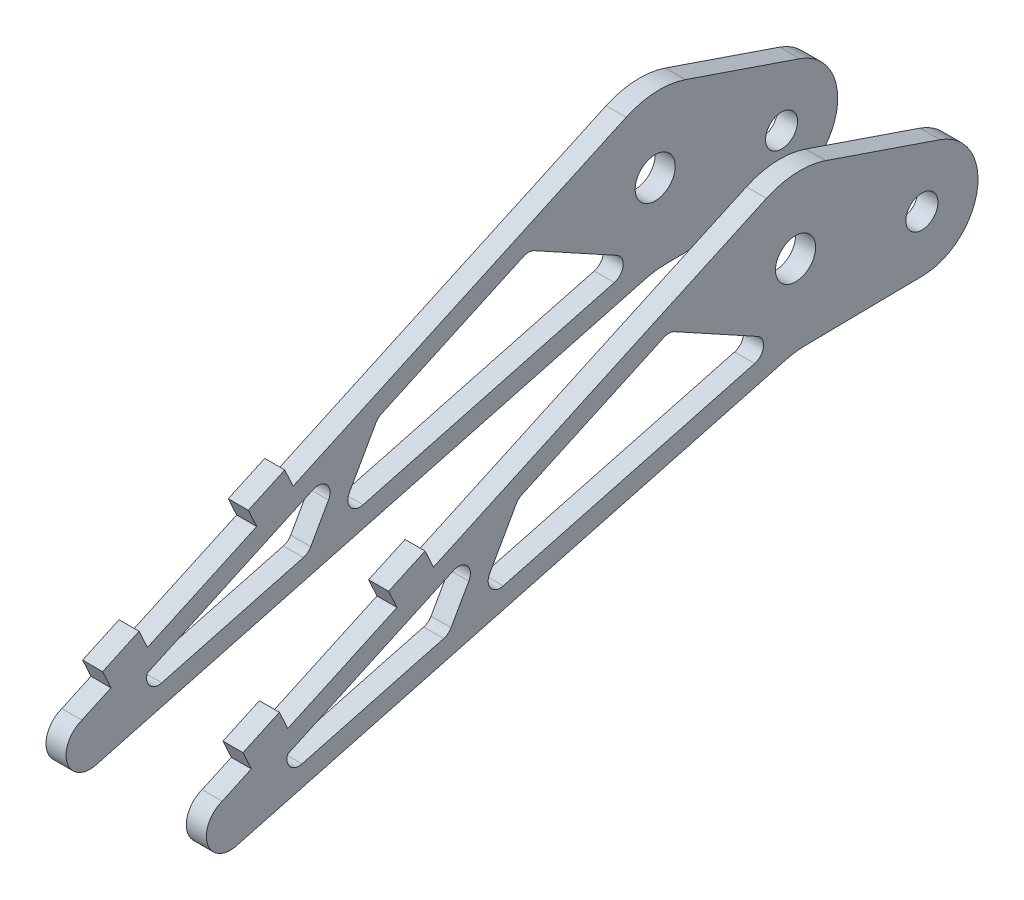
SolidWorks part; units mm, degrees
ref_plane "Front Plane" through (0, 0, 0) normal (1, 0, 0) x (0, 1, 0)
ref_plane "Top Plane" through (0, 0, 0) normal (0, 0, 1) x (0, 1, 0)
ref_plane "Right Plane" through (0, 0, 0) normal (0, 1, 0) x (-1, 0, 0)
sketch "Sketch1" plane through (0, 0, 0) normal (1, 0, 0) x (0, 1, 0)
  line L0 (0, 0) -> (5.5567, 31.5138) construction
  line L1 (5.5567, 31.5138) -> (-45.7463, 172.4677) construction
  line L2 (0, 0) -> (50000, 0) construction
  line L3 (5.5567, 31.5138) -> (-14.4433, 31.5138) construction
  line L4 (-13.9986, -0.1963) -> (-14.4433, 31.5138)
  line L5 (-14.4433, 31.5138) -> (-51.3844, 170.4156)
  line L6 (-45.7463, 172.4677) -> (-51.3844, 170.4156) construction
  line L7 (5.5567, 31.5138) -> (25.5567, 31.5138) construction
  line L8 (13.2486, -4.5247) -> (25.5567, 31.5138)
  line L9 (-45.7463, 172.4677) -> (-40.1081, 174.5199) construction
  line L10 (-40.1081, 174.5199) -> (25.5567, 31.5138)
  line L11 (0, 0) -> (-45.7463, 172.4677) construction
  line L12 (-30.4865, 111.2917) -> (-10.0592, 34.4834)
  line L13 (5.6, 62.9939) -> (-11.7181, 100.7094)
  line L14 (-11.7181, 100.7094) -> (-30.4865, 111.2917)
  line L17 (-15.2745, 108.4546) -> (-38.215, 158.4149)
  line L18 (-38.215, 158.4149) -> (-44.1163, 162.5408)
  line L19 (-44.1163, 162.5408) -> (-32.2824, 118.0442)
  line L20 (-32.2824, 118.0442) -> (-15.2745, 108.4546)
  line L21 (-10.0592, 34.4834) -> (5.6, 62.9939)
  line L22 (-17.9919, 126.3548) -> (-34.6834, 162.7058)
  line L23 (-34.6834, 162.7058) -> (-30.1395, 164.7922) construction
  line L24 (-17.9919, 126.3548) -> (-13.456, 128.4586) construction
  line L25 (-28.0531, 160.2484) -> (-32.226, 169.3361)
  line L26 (-11.3696, 123.9147) -> (-15.5425, 133.0025)
  line L27 (-32.226, 169.3361) -> (-36.7698, 167.2497)
  line L28 (-28.0531, 160.2484) -> (-32.597, 158.1619)
  line L29 (-15.5425, 133.0025) -> (-20.0863, 130.916)
  line L30 (-11.3696, 123.9147) -> (-15.9134, 121.8283)
  circle A0 centre (0, 0) radius 4
  circle A1 centre (5.5567, 31.5138) radius 5
  arc A2 (-13.9986, -0.1963) -> (13.2486, -4.5247) centre (0, 0) ccw
  arc A3 (-51.3844, 170.4156) -> (-40.1081, 174.5199) centre (-45.7463, 172.4677) cw
  arc A4 (14, 0) -> (2.4311, 13.7873) centre (0, 0) ccw construction
  arc A5 (2.4311, 13.7873) -> (-13.9986, -0.1963) centre (0, 0) ccw construction
  circle A6 centre (0, 0) radius 14 construction
  arc A7 (13.2486, -4.5247) -> (14, 0) centre (0, 0) ccw construction
  point P14 (14, 0)
  point P29 (-26.3376, 144.5303)
  point P35 (-30.1395, 164.7922)
  point P39 (-13.456, 128.4586)
  dimension "D6" = 8
  dimension "D7" = 10
  dimension "D11" = 5
  dimension "D1" = 100
  dimension "D2" = 32
  dimension "D3" = 20
  dimension "D4" = 70
  dimension "D5" = 150
  dimension "D9" = 6
  dimension "D10" = 20
  dimension "D12" = 0
  dimension "D13" = 5
  dimension "D14" = 5
  dimension "D15" = 5
  dimension "D16" = 19.525
  dimension "D17" = 5
  dimension "D18" = 40
  dimension "D19" = 5
  dimension "D20" = 10
  dimension "D21" = 33
  dimension "D8" = 10
extrude "Boss-Extrude1" add sketch "Sketch1" against normal blind 5 contours A3 L5 L4 A2 L8 L10 L22 A1 A0 L21 L12 L14 L13 L20 L19 L18 L17 | L30 L26 L29 L10 | L28 L25 L27 L10 region at (0, -12.147, 15.6879) region at (0, -15.728, 127.4154) region at (0, -32.4115, 163.749)
fillet "Fillet3" radius 20 2 edges at (-2.5, -14.4433, 31.5138) (-2.5, 25.5567, 31.5138)
ref_plane "Plane1" through (15, 0, 0) normal (1, 0, 0) x (0, 1, 0)
fillet "Fillet6" radius 3 8 edges at (-2.5, -38.215, 158.4149) (-2.5, -32.2824, 118.0442) (-2.5, -30.4865, 111.2917) (-2.5, -11.7181, 100.7094) (-2.5, -10.0592, 34.4834) (-2.5, 5.6, 62.9939) (-2.5, -15.2745, 108.4546) (-2.5, -44.1163, 162.5408)
mirror "Mirror4" about plane through (15, 0, 0) normal (1, 0, 0) of bodies 101
